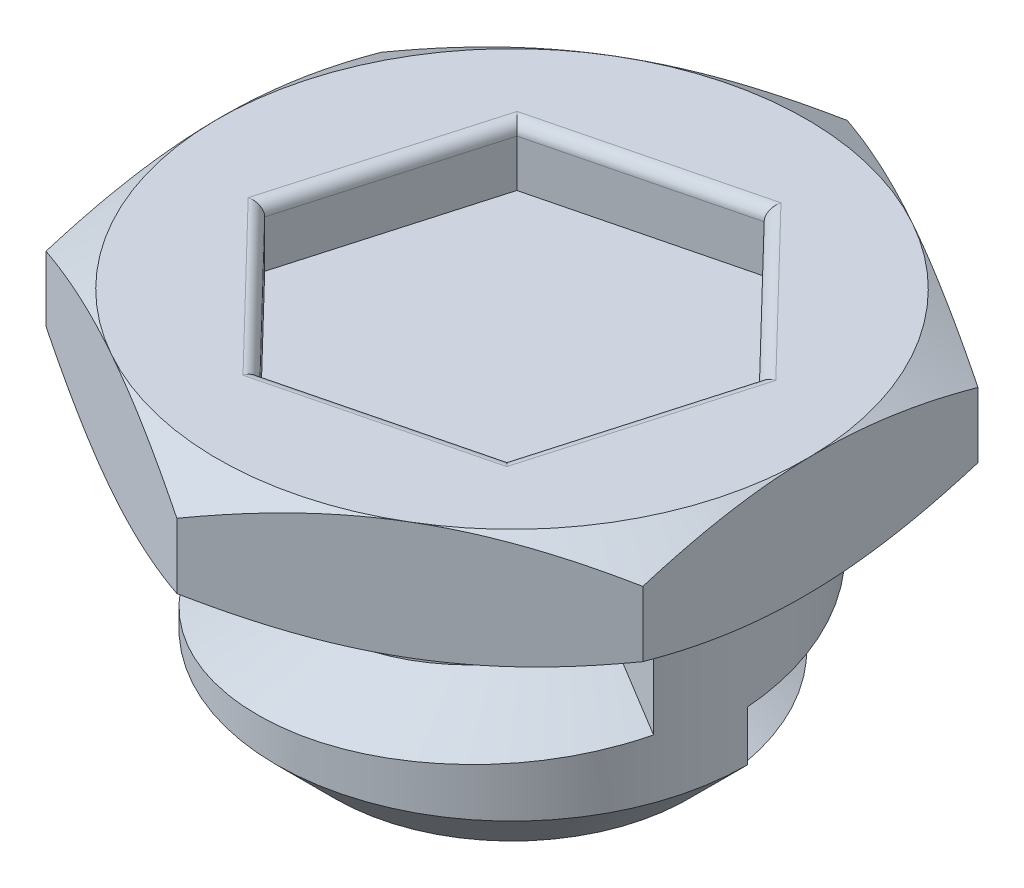
SolidWorks part; units mm, degrees
material "Stal nierdzewna (ferrytyczna)"
ref_plane "Front Plane" through (0, 0, 0) normal (0, 0, 1) x (1, 0, 0)
ref_plane "Top Plane" through (0, 0, 0) normal (0, 1, 0) x (1, 0, 0)
ref_plane "Right Plane" through (0, 0, 0) normal (1, 0, 0) x (0, 0, -1)
sketch "Szkic1" plane through (0, 0, 0) normal (0, 1, 0) x (1, 0, 0)
  circle A0 centre (0, 0) radius 2
extrude "Dodanie-wyciągnięcie1" add sketch "Szkic1" along normal blind 2
sketch "Szkic2" plane through (0, 2, 0) normal (0, 1, 0) x (1, 0, 0)
  line L1 (2.4798, 1.4778) -> (-0.0399, 2.8865)
  line L2 (-0.0399, 2.8865) -> (-2.5197, 1.4087)
  line L3 (-2.5197, 1.4087) -> (-2.4798, -1.4778)
  line L4 (-2.4798, -1.4778) -> (0.0399, -2.8865)
  line L5 (0.0399, -2.8865) -> (2.5197, -1.4087)
  line L6 (2.5197, -1.4087) -> (2.4798, 1.4778)
  circle A0 centre (0, 0) radius 2.5 construction
extrude "Dodanie-wyciągnięcie2" add sketch "Szkic2" along normal blind 1
sketch "Szkic3" plane through (0, 3, 0) normal (0, 1, 0) x (1, 0, 0)
  circle A0 centre (0, 0) radius 2.5
extrude "Wytnij-wyciągnięcie1" cut sketch "Szkic3" against normal blind 1 draft 60 flip side to cut
sketch "Szkic4" plane through (0, 2, 0) normal (0, -1, 0) x (1, 0, 0)
  circle A0 centre (0, 0) radius 2.5
extrude "Wytnij-wyciągnięcie3" cut sketch "Szkic4" against normal blind 1 draft 60 flip side to cut
sketch "Szkic5" plane through (0, 3, 0) normal (0, 1, 0) x (1, 0, 0)
  line L1 (-1.204, 1.2452) -> (-1.6803, -0.4201)
  line L2 (-1.6803, -0.4201) -> (-0.4764, -1.6653)
  line L3 (-0.4764, -1.6653) -> (1.204, -1.2452)
  line L4 (1.204, -1.2452) -> (1.6803, 0.4201)
  line L5 (1.6803, 0.4201) -> (0.4764, 1.6653)
  line L6 (0.4764, 1.6653) -> (-1.204, 1.2452)
  circle A0 centre (0, 0) radius 1.5 construction
extrude "Wytnij-wyciągnięcie4" cut sketch "Szkic5" against normal blind 0.5
fillet "Zaokrąglenie1" radius 0.1 6 edges at (0.3638, 3, 1.4552) (1.4422, 3, 0.4125) (1.0783, 3, -1.0427) (-0.3638, 3, -1.4552) (-1.4422, 3, -0.4125) (-1.0783, 3, 1.0427)
thread "Gwint2" pitch 1.0583 method cut profile "Profil gwintu2" start angle 0, offset 0, length 1, pitch 1.0583, diameter 4
ref_plane "Płaszczyzna2" through (2, 0, 0) normal (0, 0, 1) x (1, 0, 0)
sketch "Profil gwintu2" plane through (2, 0, 0) normal (0, 0, 1) x (1, 0, 0)
  line L0 (0, 0) -> (0, 1.0583) construction
  line L11 (0, 0) -> (0, 0.926)
  line L12 (0, 0.926) -> (-0.5728, 0.5953)
  line L13 (-0.5728, 0.5953) -> (-0.5728, 0.3307)
  line L15 (-0.5728, 0.3307) -> (0, 0)
  line L17 (-0.5728, 0.463) -> (0, 0.463) construction
  point P2 (0, 0)
  dimension "Pitch" = 1.0583
  dimension "Profile_Angle" = 60
  dimension "Profile_Land" = 0.2646
  dimension "Profile_Height" = 0.5728
chamfer "Sfazowanie1" distance 0.5 angle 45 1 edges at (0, 0, 2)
